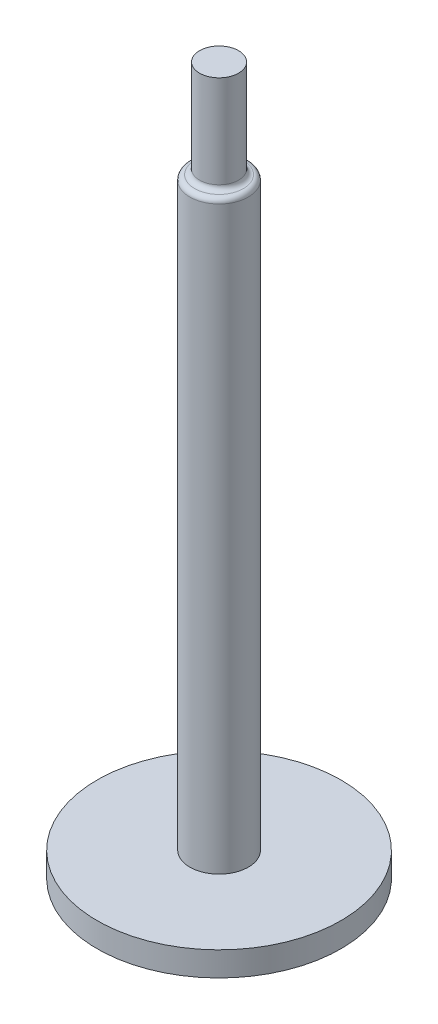
SolidWorks part; units mm, degrees
ref_plane "Front Plane" through (0, 0, 0) normal (0, 0, 1) x (1, 0, 0)
ref_plane "Top Plane" through (0, 0, 0) normal (0, 1, 0) x (1, 0, 0)
ref_plane "Right Plane" through (0, 0, 0) normal (1, 0, 0) x (0, 0, -1)
sketch "Sketch1" plane through (0, 0, 0) normal (0, 1, 0) x (1, 0, 0)
  circle A0 centre (0, 0) radius 4
  dimension "D1" = 8
extrude "Boss-Extrude1" add sketch "Sketch1" along normal mid plane 20
sketch "Sketch2" plane through (0, -10, 0) normal (0, -1, 0) x (1, 0, 0)
  circle A0 centre (0, 0) radius 6
  dimension "D1" = 12
extrude "Boss-Extrude2" add sketch "Sketch2" along normal blind 120
sketch "Sketch3" plane through (0, -130, 0) normal (0, -1, 0) x (1, 0, 0)
  circle A0 centre (0, 0) radius 25
  dimension "D1" = 50
extrude "Boss-Extrude3" add sketch "Sketch3" along normal blind 5
sketch "Sketch4" plane through (0, -135, 0) normal (0, -1, 0) x (1, 0, 0)
  circle A0 centre (0, 0) radius 6
  dimension "1.2" = 12
extrude "Boss-Extrude4" add sketch "Sketch4" along normal blind 5
fillet "Fillet2" radius 1 2 edges at (0, -10, 4) (0, -10, -6)
